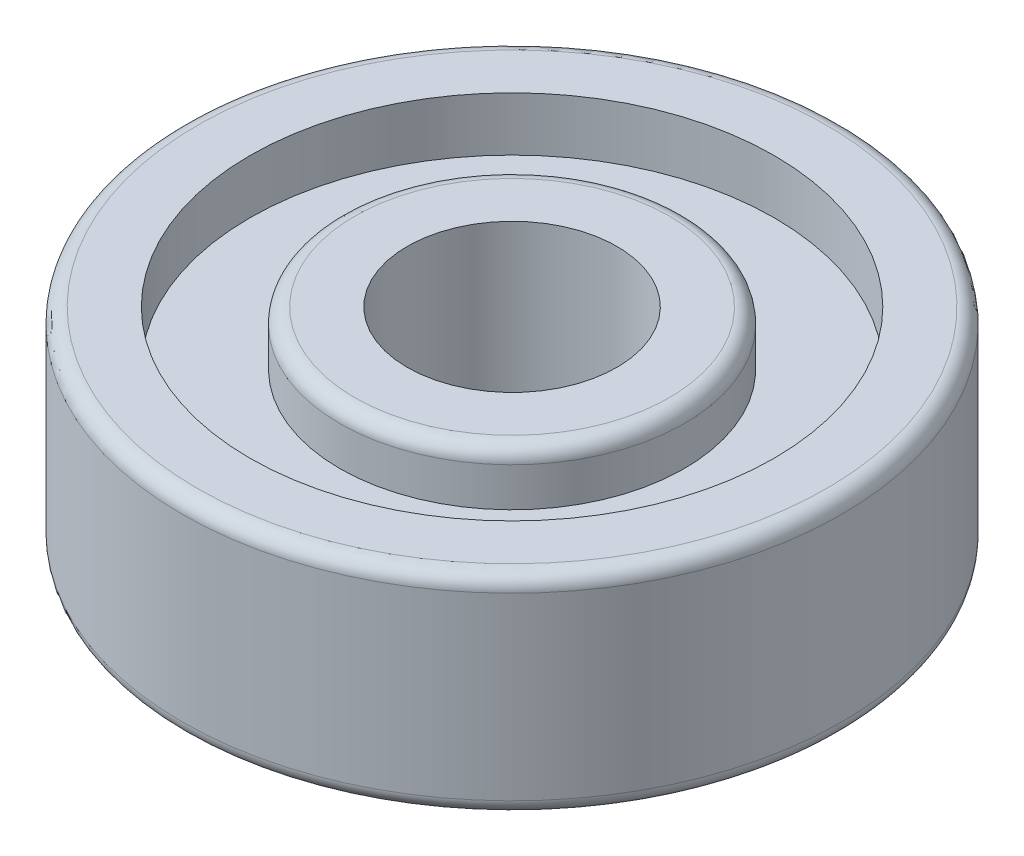
SolidWorks part; units mm, degrees
ref_plane "Front Plane" through (0, 0, 0) normal (0, 0, 1) x (1, 0, 0)
ref_plane "Top Plane" through (0, 0, 0) normal (0, 1, 0) x (1, 0, 0)
ref_plane "Right Plane" through (0, 0, 0) normal (1, 0, 0) x (0, 0, -1)
sketch "Sketch1" plane through (0, 0, 0) normal (0, 1, 0) x (1, 0, 0)
  circle A0 centre (0, 0) radius 11
  dimension "D1" = 22
extrude "Boss-Extrude1" add sketch "Sketch1" along normal mid plane 7
sketch "Sketch3" plane through (0, 3.5, 0) normal (0, 1, 0) x (1, 0, 0)
  circle A0 centre (0, 0) radius 3.5
  circle A1 centre (0, 0) radius 8.75
  circle A2 centre (0, 0) radius 5.75
  dimension "D1" = 7
  dimension "D2" = 17.5
  dimension "D3" = 2.25
extrude "Cut-Extrude1" cut sketch "Sketch3" against normal through all contours A0
extrude "Cut-Extrude2" cut sketch "Sketch3<3>" against normal blind 1.8 contours A1 A2 region at (-8.5025, 3.5, 0)
sketch "Sketch3<3>" plane through (0, 3.5, 0) normal (0, 1, 0) x (1, 0, 0) same geometry as "Sketch3"
mirror "Mirror1" about plane through (0, 0, 0) normal (0, 1, 0) of "Cut-Extrude2"
fillet "Fillet1" radius 0.5 4 edges at (0, 3.5, 5.75) (0, 3.5, 11) (0, -3.5, 5.75) (0, -3.5, 11)
